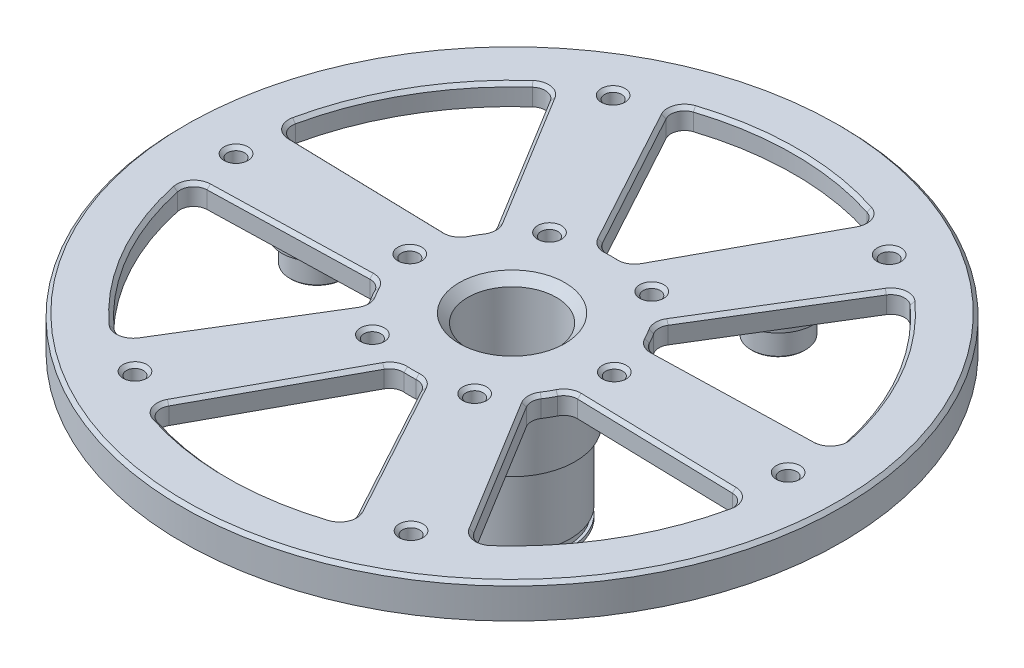
SolidWorks part; units mm, degrees
ref_plane "Front Plane" through (0, 0, 0) normal (0, 0, 1) x (1, 0, 0)
ref_plane "Top Plane" through (0, 0, 0) normal (0, 1, 0) x (1, 0, 0)
ref_plane "Right Plane" through (0, 0, 0) normal (1, 0, 0) x (0, 0, -1)
ref_axis "Axis1" through (0, 0, 0) along (0, 1, 0)
sketch "Sketch1" plane through (0, 0, 0) normal (0, 0, 1) x (1, 0, 0)
  line L0 (0, 0) -> (0, -50000) construction
  line L1 (-6.5, 18.1) -> (-6.5, -1.95)
  line L3 (-6.5, -1.95) -> (-4.5, -1.95)
  line L4 (-4.5, -1.95) -> (-4.5, -3.95)
  line L5 (-6.6, -3.95) -> (-6.6, -6.45)
  line L10 (-8.5, 18.1) -> (-6.5, 18.1)
  line L11 (-8.5, -6.45) -> (-8.5, 18.1)
  line L19 (-6.6, -3.95) -> (-4.5, -3.95)
  line L27 (6.3, 17.6) -> (-6.3, 17.6) construction
  line L28 (-6.6, -6.45) -> (-8.5, -6.45)
  line L30 (13.02, -4.15) -> (-13.02, -4.15) construction
  dimension "D1" = 2
  dimension "D2" = 17
  dimension "D3" = 0.5
  dimension "D4" = 6.5
  dimension "D5" = 2
  dimension "D6" = 2.5
  dimension "D8" = 2.3
  dimension "D9" = 13.2
revolve "Shaft" add sketch "Sketch1" angle 360 about L0
sketch "Sketch2" plane through (0, 0, 0) normal (0, 0, 1) x (1, 0, 0)
  line L1 (-8.5, 18.1) -> (-9.25, 18.1)
  line L2 (10.2326, 5.85) -> (-10.2326, 5.85) construction
  line L3 (-9.25, 5.85) -> (-8.5, 5.85)
  line L4 (-8.5, 5.85) -> (-8.5, 18.1)
  line L5 (-9.25, 5.85) -> (-9.25, 18.1)
  line L7 (8.5, 18.1) -> (-8.5, 18.1) construction
  line L14 (-8.5, 18.1) -> (-8.5, -6.45) construction
  dimension "D1" = 0.75
revolve "Revolve1" add sketch "Sketch2" angle 360 about axis through (0, 0, 0) along (0, 1, 0)
ref_plane "Plane1" through (0, 16.65, 0) normal (0, 1, 0) x (1, 0, 0)
sketch "Sketch4" plane through (0, 0, 0) normal (0, 0, 1) x (1, 0, 0)
  line L0 (-28.599, 12.1363) -> (-28.599, -49987.8637) construction
  line L1 (-28.599, 12) -> (-28.599, 18.1)
  line L2 (-28.599, 18.1) -> (-33.799, 18.1)
  line L3 (-33.799, 18.1) -> (-33.799, 16)
  line L4 (-33.799, 16) -> (-32.599, 16)
  line L5 (-32.599, 16) -> (-32.599, 12)
  line L6 (-32.599, 12) -> (-28.599, 12)
  line L8 (8.5, 18.1) -> (-8.5, 18.1) construction
  line L9 (11.5, 16) -> (-11.5, 16) construction
  dimension "D1" = 28.599
  dimension "D2" = 8
  dimension "D3" = 1.2
  dimension "D5" = 4
revolve "Revolve2" add sketch "Sketch4" angle 360 about L0
pattern_circular "CirPattern2" count 3 over 360 about axis through (0, 0, 0) along (0, 1, 0) of bodies 103
sketch "Sketch8" plane through (0, 0, 0) normal (0, 0, 1) x (1, 0, 0)
  line L1 (-48.35, 20.1) -> (-6.5, 20.1)
  line L2 (-6.5, 20.1) -> (-6.5, 17.1)
  line L3 (-6.5, 17.1) -> (-42.52, 17.1)
  line L5 (-42.52, 17.1) -> (-42.52, 18.1)
  line L7 (-48.35, 15.15) -> (-48.35, 20.1)
  line L9 (-43.52, 17.65) -> (-43.52, 16.65) construction
  line L10 (-47.35, 18.1) -> (-47.35, 15.15)
  line L11 (-47.35, 15.15) -> (-48.35, 15.15)
  line L12 (-48.35, 0) -> (-48.35, -9.6235) construction
  line L13 (9.25, 18.1) -> (-9.25, 18.1) construction
  line L14 (48.35, 14.15) -> (-48.35, 14.15) construction
  line L15 (-47.35, 18.1) -> (-42.52, 18.1)
  dimension "D1" = 3
  dimension "D2" = 1
  dimension "D3" = 1
  dimension "D4" = 1
  dimension "D5" = 1
  dimension "D6" = 1
revolve "Revolve3" add sketch "Sketch8" angle 360 about axis through (0, 0, 0) along (0, 1, 0)
hole_wizard "M3x0.5 Tapped Hole1" [suppressed] positions "Sketch9" profile "Sketch10" tap size "M3x0.5" standard "ANSI Metric"
sketch "Sketch9" plane through (0, 12.65, 0) normal (0, -1, 0) x (-1, 0, 0)
  point P0 (-14, 24.2487)
  point P3 (28, 0)
  point P6 (-14, -24.2487)
sketch "Sketch10" plane through (14, 12.65, -24.2487) normal (1, 0, 0) x (0, 0, -1)
  line L0 (0, 0) -> (0, 7.95)
  line L1 (0, 7.95) -> (1.25, 7.95)
  line L2 (1.25, 7.95) -> (1.25, 0)
  line L5 (1.25, 0) -> (0, 0)
  line L11 (0, -6.35) -> (0, 107.95) construction
  dimension "Thru Tap Drill Dia." = 2.5
  dimension "Thru Tap Drill Depth" = 7.95
cosmetic thread "Hole Thread2" [suppressed] parameters "D2"=3
cosmetic thread "Hole Thread3" [suppressed] parameters "D2"=3
cosmetic thread "Hole Thread4" [suppressed] parameters "D2"=3
chamfer "Chamfer1" distance 1.25 angle 45 1 edges at (0, 20.1, -6.5)
hole_wizard "M3x0.5 Tapped Hole - 60 mm diameter" positions "Sketch11" profile "Sketch12" tap size "M3x0.5" standard "ANSI Metric" end condition through all
sketch "Sketch11" plane through (0, 20.1, 0) normal (0, 1, 0) x (1, 0, 0)
  line L5 (0, 0) -> (-50000, 0) construction
  circle A1 centre (0, 0) radius 15 construction
  circle A2 centre (0, 0) radius 20 construction
  circle A3 centre (0, 0) radius 40.5 construction
  point P131 (-40.5, 0)
  point P132 (-15, 0)
  dimension "D1" = 30
  dimension "D2" = 40
  dimension "D3" = 81
sketch "Sketch12" plane through (-15, 20.1, 0) normal (1, 0, 0) x (0, 0, 1)
  line L0 (0, 0) -> (0, 26.55)
  line L1 (0, 26.55) -> (1.25, 26.55)
  line L2 (1.25, 26.55) -> (1.25, 0.5)
  line L3 (1.25, 0.5) -> (1.75, 0)
  line L5 (1.75, 0) -> (0, 0)
  line L6 (-1.25, 0.5) -> (-1.75, 0) construction
  line L11 (0, -6.35) -> (0, 107.95) construction
  dimension "Thru Tap Drill Dia." = 2.5
  dimension "Thru Tap Drill Depth" = 26.55
  dimension "Near C'Sink Dia." = 3.5
  dimension "Near C'Sink Angle" = 90
cosmetic thread "Hole Thread6" parameters "D2"=3
cosmetic thread "Hole Thread7" parameters "D2"=3
pattern_circular "CirPattern3" count 6 over 360 about axis through (0, 0, 0) along (0, 1, 0) of "M3x0.5 Tapped Hole - 60 mm diameter"
sketch "Sketch13" plane through (0, 0, 0) normal (0, 1, 0) x (1, 0, 0)
  line L0 (0, 0) -> (0, -50000) construction
  line L1 (-13.8834, -36.4796) -> (-2.7571, -16.0152)
  line L2 (13.8834, -36.4796) -> (2.7571, -16.0152)
  arc A0 (-12.7426, -39.3376) -> (12.7426, -39.3376) centre (0, 0) ccw
  arc A1 (-0.8824, -14.974) -> (0.8824, -14.974) centre (0, 0) ccw
  arc A2 (-0.8824, -14.974) -> (-2.7571, -16.0152) centre (-1, -16.9706) ccw
  arc A3 (0.8824, -14.974) -> (2.7571, -16.0152) centre (1, -16.9706) cw
  arc A4 (12.7426, -39.3376) -> (13.8834, -36.4796) centre (12.1263, -37.4349) ccw
  arc A5 (-12.7426, -39.3376) -> (-13.8834, -36.4796) centre (-12.1263, -37.4349) cw
  circle A8 centre (0, 0) radius 48.35 construction
  point P11 (-2.123, -14.849)
  point P14 (2.123, -14.849)
  point P17 (15, -38.5334)
  point P20 (-15, -38.5334)
  dimension "D1" = 2
  dimension "D3" = 15
  dimension "D4" = 7
  dimension "D2" = 30
  dimension "D5" = 2
extrude "Cut-Extrude1" cut sketch "Sketch13" along normal through all
pattern_circular "CirPattern4" count 6 over 360 about axis through (0, 0, 0) along (0, 1, 0) of "Cut-Extrude1"
chamfer "Chamfer2" distance 0.5 angle 45 48 edges at (-26.8911, 20.1, 5.9182) (-40.0536, 20.1, 6.9779) (-14.1683, 20.1, 5.9041) (-12.9904, 20.1, 7.5) (-26.0698, 20.1, 31.1985) (-12.1972, 20.1, 9.3181) (-18.5708, 20.1, 20.3293) (-8.3202, 20.1, 26.2474) (-13.9838, 20.1, 38.1764) (-1.9711, 20.1, 15.2221) (0, 20.1, 15) (13.9838, 20.1, 38.1764) (1.9711, 20.1, 15.2221) (8.3202, 20.1, 26.2474) (18.5708, 20.1, 20.3293) (26.0698, 20.1, 31.1985) (12.1972, 20.1, 9.3181) (12.9904, 20.1, 7.5) (40.0536, 20.1, 6.9779) (14.1683, 20.1, 5.9041) (26.8911, 20.1, 5.9182) (26.8911, 20.1, -5.9182) (40.0536, 20.1, -6.9779) (14.1683, 20.1, -5.9041) (12.9904, 20.1, -7.5) (26.0698, 20.1, -31.1985) (12.1972, 20.1, -9.3181) (18.5708, 20.1, -20.3293) (8.3202, 20.1, -26.2474) (13.9838, 20.1, -38.1764) (1.9711, 20.1, -15.2221) (0, 20.1, -15) (-13.9838, 20.1, -38.1764) (-1.9711, 20.1, -15.2221) (-8.3202, 20.1, -26.2474) (-26.8911, 20.1, -5.9182) (-14.1683, 20.1, -5.9041) (-40.0536, 20.1, -6.9779) (-12.9904, 20.1, -7.5) (-12.1972, 20.1, -9.3181) (-26.0698, 20.1, -31.1985) (-18.5708, 20.1, -20.3293) (-35.8102, 20.1, 20.675) (0, 20.1, 41.35) (35.8102, 20.1, 20.675) (35.8102, 20.1, -20.675) (0, 20.1, -41.35) (-35.8102, 20.1, -20.675)
chamfer "Chamfer3" distance 0.5 angle 45 1 edges at (0, 20.1, -48.35)
sketch "Sketch14" plane through (0, 0, 0) normal (0, 0, 1) x (1, 0, 0)
  line L0 (0, 0) -> (0, -50000) construction
  line L1 (-14.652, -4.35) -> (-8.1, -4.35)
  line L2 (-14.652, -4.35) -> (-14.652, -5.45)
  line L3 (-14.652, -5.45) -> (-8.1, -5.45)
  line L4 (-8.1, -4.35) -> (-8.1, -5.45)
  line L7 (-8.5, -6.45) -> (8.5, -6.45) construction
  dimension "D1" = 16.2
  dimension "D2" = 1.1
  dimension "D3" = 1
revolve "Cut-Revolve1" cut sketch "Sketch14" angle 360 about L0
chamfer "Chamfer4" distance 0.5 angle 45 1 edges at (0, -6.45, 8.5)
chamfer "Chamfer5" distance 0.2 angle 45 3 edges at (16.2995, 12, -28.2316) (16.2995, 12, 28.2316) (-32.599, 12, 0)
